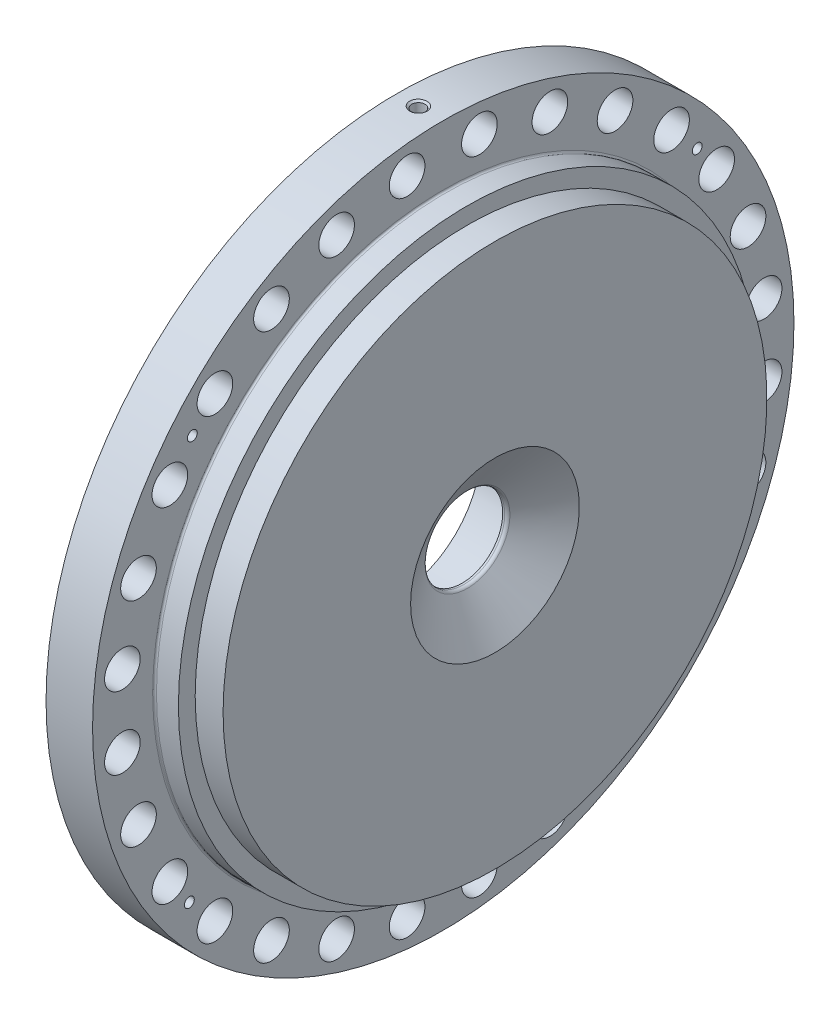
SolidWorks part; units mm, degrees
other "Markup1"
sketch "Sketch22" plane through (-5.9944, 281.051, 281.051) normal (-0.6486, 0.3883, 0.6546) x (0.7525, 0.1979, 0.6281)
material "CD4Mc-U Duplex Stainless Steel"
ref_plane "Front Plane" through (0, 0, 0) normal (0, 0, 1) x (1, 0, 0)
ref_plane "Top Plane" through (0, 0, 0) normal (0, 1, 0) x (1, 0, 0)
ref_plane "Right Plane" through (0, 0, 0) normal (1, 0, 0) x (0, 0, -1)
sketch "Sketch1" plane through (0, 0, 0) normal (0, 0, 1) x (1, 0, 0)
  line L13 (-4.7752, 67.5132) -> (-4.7752, 180.9496)
  line L14 (-4.7752, 281.051) -> (32.512, 281.051)
  line L15 (32.512, 281.051) -> (32.512, 231.3686)
  line L16 (32.512, 231.3686) -> (51.6128, 231.3686)
  line L17 (51.6128, 231.3686) -> (51.6128, 217.9066)
  line L18 (51.6128, 217.9066) -> (73.9648, 217.9066)
  line L19 (73.9648, 217.9066) -> (73.9648, 67.6275)
  line L22 (0, 0) -> (159.4613, 0) construction
  line L27 (-4.7752, 228.9937) -> (0, 228.9937)
  line L28 (0, 228.9937) -> (0, 180.9496)
  line L29 (0, 180.9496) -> (-4.7752, 180.9496)
  line L30 (-4.7752, 228.9937) -> (-4.7752, 281.051)
  line L32 (-4.7752, 67.5132) -> (47.625, 67.5132)
  line L35 (47.625, 67.5132) -> (47.625, 32.5628)
  line L36 (47.625, 32.5628) -> (49.2384, 32.5628)
  line L37 (51.8928, 33.9958) -> (73.9648, 67.6275)
  arc A0 (49.2384, 32.5628) -> (51.8928, 33.9958) centre (49.2384, 35.7378) ccw
  point P18 (50.9524, 32.5628)
  dimension "D10" = 3.175
  dimension "D1" = 78.74
  dimension "D2" = 41.4528
  dimension "D3" = 19.1008
  dimension "D4" = 3.3274
  dimension "D5" = 281.051
  dimension "D6" = 228.9937
  dimension "D7" = 231.3686
  dimension "D8" = 217.9066
  dimension "D9" = 180.9496
  dimension "D11" = 4.7752
  dimension "D12" = 32.5628
  dimension "D13" = 52.4002
  dimension "D14" = 67.5132
  dimension "D16" = 67.6275
revolve "Revolve1" add sketch "Sketch1" angle 360 about L22
sketch "Sketch4" plane through (-4.7752, 0, 0) normal (-1, 0, 0) x (0, 0, 1)
  line L0 (0, 0) -> (0, 281.051) construction
  line L1 (0, 0) -> (28.9721, 257.1355) construction
  circle A1 centre (28.9721, 257.1355) radius 14.2875
  circle A2 centre (0, 0) radius 258.7625 construction
  dimension "D2" = 28.575
  dimension "D3" = 517.525
  dimension "D1" = 6.429
extrude "Cut-Extrude1" cut sketch "Sketch4" against normal through all
pattern_circular "CirPattern2" count 28 over 360 about axis through (-4.7752, 0, 0) along (-1, 0, 0) of "Cut-Extrude1"
sketch "Sketch5" plane through (0, 0, 0) normal (-1, 0, 0) x (0, 0, 1)
  line L0 (0, 0) -> (53.4138, 199.3429) construction
  line L2 (0, 0) -> (0, 281.051) construction
  circle A0 centre (0, 0) radius 206.375 construction
  circle A1 centre (53.4138, 199.3429) radius 9.525
  circle A3 centre (0, 0) radius 281.051 construction
  dimension "D1" = 412.75
  dimension "D3" = 19.05
  dimension "D2" = 15
hole_wizard "3/4-10 Tapped Hole1" positions "Sketch7" profile "Sketch8" tap size "3/4-10" standard "ANSI Inch"
sketch "Sketch7" plane through (0, 0, 0) normal (-1, 0, 0) x (0, 0, 1)
  point P0 (53.4138, 199.3429)
sketch "Sketch8" plane through (0, 199.3429, 53.4138) normal (0, 1, 0) x (0, 0, 1)
  line L0 (0, 0) -> (0, 30.4074)
  line L1 (0, 30.4074) -> (8.3337, 25.4)
  line L2 (8.3337, 25.4) -> (8.3337, 1.8263)
  line L3 (8.3337, 1.8263) -> (10.16, 0)
  line L5 (10.16, 0) -> (0, 0)
  line L6 (-8.3337, 1.8263) -> (-10.16, 0) construction
  line L10 (0, 30.4074) -> (-8.3337, 25.4) construction
  line L11 (0, -6.35) -> (0, 107.95) construction
  dimension "Tap Drill Dia." = 16.6675
  dimension "Tap Drill Depth" = 25.4
  dimension "Near C'Sink Dia." = 20.32
  dimension "Near C'Sink Angle" = 90
  dimension "Drill Angle" = 118
cosmetic thread "Hole Thread2" parameters "D1"=12.7, "D2"=19.05
pattern_circular "CirPattern3" count 12 over 360 about axis through (47.625, 0, 0) along (-1, 0, 0) of "3/4-10 Tapped Hole1"
cosmetic thread "Hole Thread3" parameters "D1"=12.7, "D2"=19.05
cosmetic thread "Hole Thread4" parameters "D1"=12.7, "D2"=19.05
cosmetic thread "Hole Thread5" parameters "D1"=12.7, "D2"=19.05
cosmetic thread "Hole Thread6" parameters "D1"=12.7, "D2"=19.05
cosmetic thread "Hole Thread7" parameters "D1"=12.7, "D2"=19.05
cosmetic thread "Hole Thread8" parameters "D1"=12.7, "D2"=19.05
cosmetic thread "Hole Thread9" parameters "D1"=12.7, "D2"=19.05
cosmetic thread "Hole Thread10" parameters "D1"=12.7, "D2"=19.05
cosmetic thread "Hole Thread11" parameters "D1"=12.7, "D2"=19.05
cosmetic thread "Hole Thread12" parameters "D1"=12.7, "D2"=19.05
cosmetic thread "Hole Thread13" parameters "D1"=12.7, "D2"=19.05
sketch "Sketch9" plane through (-4.7752, 0, 0) normal (-1, 0, 0) x (0, 0, 1)
  line L0 (0, 0) -> (0, 94.996) construction
  line L1 (0, 0) -> (67.1723, 67.1723) construction
  circle A0 centre (0, 0) radius 94.996 construction
  circle A1 centre (67.1723, 67.1723) radius 11.1125
  dimension "D1" = 189.992
  dimension "D3" = 22.225
  dimension "D2" = 45
hole_wizard "7/8-9 Tapped Hole1" positions "3DSketch1" profile "Sketch10" tap size "7/8-9" standard "ANSI Inch"
sketch3d "3DSketch1"
  point P0 (-4.7752, 67.1723, 67.1723)
sketch "Sketch10" plane through (-4.7752, 67.1723, 67.1723) normal (0, 1, 0) x (0, 0, 1)
  line L0 (0, 0) -> (0, 31.2422)
  line L1 (0, 31.2422) -> (9.7231, 25.4)
  line L2 (9.7231, 25.4) -> (9.7231, 2.0244)
  line L3 (9.7231, 2.0244) -> (11.7475, 0)
  line L5 (11.7475, 0) -> (0, 0)
  line L6 (-9.7231, 2.0244) -> (-11.7475, 0) construction
  line L10 (0, 31.2422) -> (-9.7231, 25.4) construction
  line L11 (0, -6.35) -> (0, 107.95) construction
  dimension "Tap Drill Dia." = 19.4462
  dimension "Tap Drill Depth" = 25.4
  dimension "Near C'Sink Dia." = 23.495
  dimension "Near C'Sink Angle" = 90
  dimension "Drill Angle" = 118
cosmetic thread "Hole Thread14" parameters "D1"=44.45, "D2"=22.225
pattern_circular "CirPattern4" count 4 over 360 about axis through (47.625, 0, 0) along (-1, 0, 0) of "7/8-9 Tapped Hole1"
cosmetic thread "Hole Thread15" parameters "D1"=44.45, "D2"=22.225
cosmetic thread "Hole Thread16" parameters "D1"=44.45, "D2"=22.225
cosmetic thread "Hole Thread17" parameters "D1"=44.45, "D2"=22.225
sketch "Sketch11" plane through (-4.7752, 0, 0) normal (-1, 0, 0) x (0, 0, 1)
  line L0 (0, 0) -> (201.0962, 162.8445) construction
  line L1 (0, 0) -> (258.7625, 0) construction
  circle A0 centre (0, 0) radius 258.7625 construction
  circle A2 centre (201.0962, 162.8445) radius 4.7625
  dimension "D1" = 517.525
  dimension "D3" = 9.525
  dimension "D2" = 39
hole_wizard "Tap Drill for 3/8-16 Tap1" positions "3DSketch9" profile "Sketch21" hole size "3/8-16" standard "ANSI Inch"
sketch3d "3DSketch9"
  point P0 (-4.7752, 162.8445, 201.0962)
sketch "Sketch21" plane through (-4.7752, 162.8445, 201.0962) normal (0, 1, 0) x (0, 0, 1)
  line L0 (0, 0) -> (0, 43.0247)
  line L1 (0, 43.0247) -> (3.9687, 40.64)
  line L2 (3.9687, 40.64) -> (3.9687, 0.635)
  line L3 (3.9687, 0.635) -> (4.6037, 0)
  line L5 (4.6037, 0) -> (0, 0)
  line L6 (-3.9687, 0.635) -> (-4.6037, 0) construction
  line L10 (0, 43.0247) -> (-3.9688, 40.64) construction
  line L11 (0, -6.35) -> (0, 107.95) construction
  dimension "Hole Dia." = 7.9375
  dimension "Hole Depth" = 40.64
  dimension "Near C'Sink Dia." = 9.2075
  dimension "Near C'Sink Angle" = 90
  dimension "Drill Angle" = 118
ref_plane "Plane2" through (0, 281.051, 0) normal (0, 1, 0) x (1, 0, 0)
sketch "Sketch20" plane through (0, 281.051, 0) normal (0, 1, 0) x (1, 0, 0)
  line L0 (-4.7752, 0) -> (12.5984, 0) construction
  line L1 (-4.7752, 281.051) -> (-4.7752, -281.051) construction
  dimension "D1" = 17.3736
pattern_circular "CirPattern5" count 56 over 360 about axis through (0, 0, 0) along (-1, 0, 0) skipping 1, 2, 3, 4, 5, 6, 7, 8, 9, 10, 11, 12, 13, 14, 15, 17, 18, 19, 20, 21, 22, 23, 24, 25, 26, 27, 29, 30, 31, 32, 33, 34, 35, 36, 37, 38, 39, 40, 41, 42, 43, 45, 46, 47, 48, 49, 50, 51, 52, 53, 54, 55 of "Tap Drill for 3/8-16 Tap1"
hole_wizard "1/2-13 Tapped Hole4" positions "3DSketch8" profile "Sketch19" tap size "1/2-13" standard "ANSI Inch"
sketch3d "3DSketch8"
  point P0 (12.5984, 281.051, 0)
sketch "Sketch19" plane through (12.5984, 281.051, 0) normal (1, 0, 0) x (0, 0, 1)
  line L0 (0, 0) -> (0, 38.2715)
  line L1 (0, 38.2715) -> (5.3581, 35.052)
  line L2 (5.3581, 35.052) -> (5.3581, 1.3651)
  line L3 (5.3581, 1.3651) -> (6.985, 0)
  line L5 (6.985, 0) -> (0, 0)
  line L6 (-5.3581, 1.3651) -> (-6.985, 0) construction
  line L10 (0, 38.2715) -> (-5.3581, 35.052) construction
  line L11 (0, -6.35) -> (0, 107.95) construction
  dimension "Tap Drill Dia." = 10.7163
  dimension "Tap Drill Depth" = 35.052
  dimension "Near C'Sink Dia." = 13.97
  dimension "Near C'Sink Angle" = 100
  dimension "Drill Angle" = 118
cosmetic thread "Hole Thread24" parameters "D1"=25.4, "D2"=12.7
fillet "Fillet1" radius 1.524 1 edges at (32.512, 0, 231.3686)
fillet "Fillet2" radius 4.7752 1 edges at (0, 0, 228.9937)
fillet "Fillet3" radius 1.524 1 edges at (0, 0, 180.9496)
